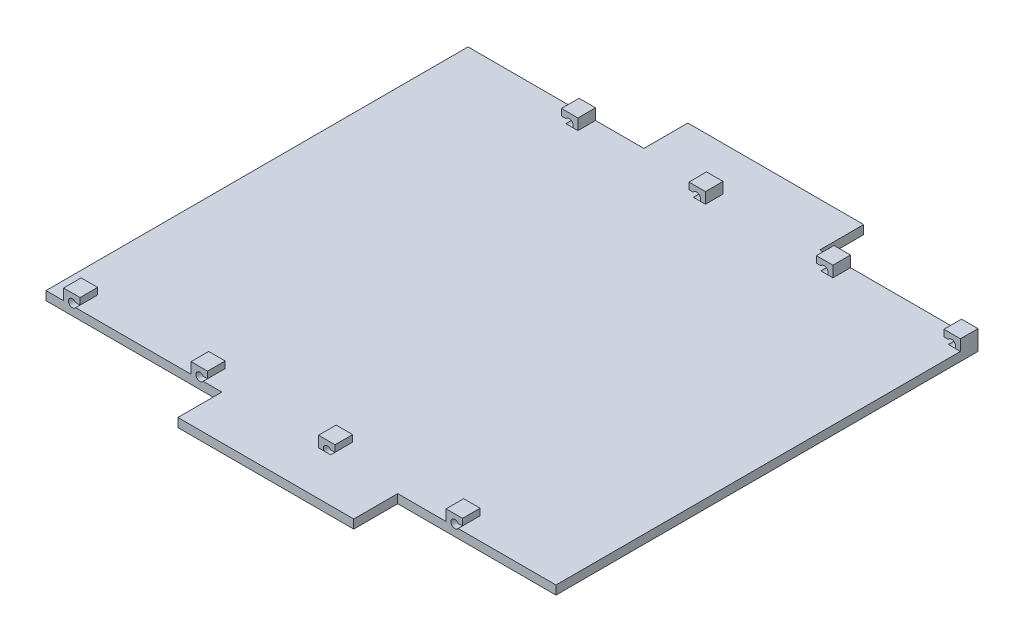
SolidWorks part; units mm, degrees
ref_plane "Front Plane" through (0, 0, 0) normal (0, 0, 1) x (1, 0, 0)
ref_plane "Top Plane" through (0, 0, 0) normal (0, 1, 0) x (1, 0, 0)
ref_plane "Right Plane" through (0, 0, 0) normal (1, 0, 0) x (0, 0, -1)
sketch "Sketch1" plane through (0, 0, 0) normal (0, 1, 0) x (1, 0, 0)
  line L0 (-18, -58) -> (-18, -48)
  line L1 (58, -48) -> (22, -48)
  line L2 (58, -48) -> (58, 48)
  line L3 (58, 48) -> (22, 48)
  line L4 (-58, -48) -> (-58, 48)
  line L5 (58, -48) -> (-58, 48) construction
  line L6 (58, 48) -> (-58, -48) construction
  line L7 (-18, -58) -> (22, -58)
  line L9 (22, -58) -> (22, -48)
  line L10 (-18, -58) -> (22, -48) construction
  line L11 (-18, -48) -> (22, -58) construction
  line L12 (2, -53) -> (2, 0) construction
  line L13 (-18, -48) -> (-58, -48)
  line L14 (2, 0) -> (-33.9675, 0) construction
  line L15 (-18, 48) -> (22, 58) construction
  line L16 (-18, 58) -> (22, 48) construction
  line L17 (22, 58) -> (22, 48)
  line L18 (-18, 58) -> (22, 58)
  line L19 (-18, 58) -> (-18, 48)
  line L20 (-18, 48) -> (-58, 48)
  point P0 (0, 0)
  point P7 (2, -53)
  dimension "D1" = 96
  dimension "D2" = 116
  dimension "D3" = 40
  dimension "D4" = 10
  dimension "D5" = 2
extrude "Boss-Extrude1" add sketch "Sketch1" along normal blind 2
sketch "Sketch2" plane through (0, 0, -48) normal (0, 0, -1) x (-1, 0, 0)
  line L0 (-58, 2) -> (-58, 4.5)
  line L1 (-58, 4.5) -> (-54.2517, 4.5)
  line L2 (-54.2517, 4.5) -> (-54.2517, 3)
  line L3 (-54.2517, 3) -> (-55.2517, 3)
  line L4 (-58, 2) -> (-22, 2) construction
  line L5 (-55.2517, 3) -> (-55.2517, 2) construction
  line L6 (-55.2517, 2) -> (-54.2517, 2)
  line L7 (-54.2517, 2) -> (-54.2517, 0)
  line L8 (-58, 0) -> (-22, 0) construction
  line L9 (-54.2517, 0) -> (-58, 0)
  line L10 (-58, 0) -> (-58, 2)
  line L11 (-55.2517, 3) -> (-55.2517, 2)
  arc A0 (-55.2517, 3) -> (-55.2517, 2) centre (-56, 2.5) ccw
  line M11 (-58, 0) -> (-22, 0)
  line M13 (-22, 2) -> (-58, 2)
  line M14 (-58, 2) -> (-58, 0)
  dimension "D1" = 0.9
  dimension "D2" = 1
  dimension "D3" = 2
  dimension "D4" = 2
  dimension "D5" = 1
extrude "Boss-Extrude2" add sketch "Sketch2" against normal blind 4 contours A0 L3 L2 L1 L0 M13 | A0 L7 M13 M14 M11 region at (56.1333, 0.9502, -48) region at (56.3692, 3.5628, -48)
extrude "Cut-Extrude1" cut sketch "Sketch2<3>" against normal blind 4 contours A0 M13 region at (56, 1.8365, -48)
sketch "Sketch2<3>" plane through (0, 0, -48) normal (0, 0, -1) x (-1, 0, 0) same geometry as "Sketch2"
sketch "Sketch3" plane through (0, 2, 0) normal (0, 1, 0) x (1, 0, 0)
  line L0 (56, 44) -> (45.5, 44) construction
  line L1 (55.2517, 44) -> (56.7483, 44) construction
  line L2 (45.5, 48) -> (45.5, -48) construction
  line L3 (55.2517, 48) -> (22, 48) construction
  line L4 (22, -48) -> (58, -48) construction
  point P10 (45.5, 0)
  dimension "D1" = 10.5
ref_axis "Axis1" through (45.5, 2, 0) along (0, 1, 0)
pattern_circular "CirPattern1" count 2 over 360 about axis through (45.5, 2, 0) along (0, 1, 0) of "Boss-Extrude2", "Cut-Extrude1"
pattern_linear "LPattern4" count 4 spacing 29 along (-1, 0, 0) of "CirPattern1", "Cut-Extrude1", "Boss-Extrude2"
equation "\"spa\"=24"
